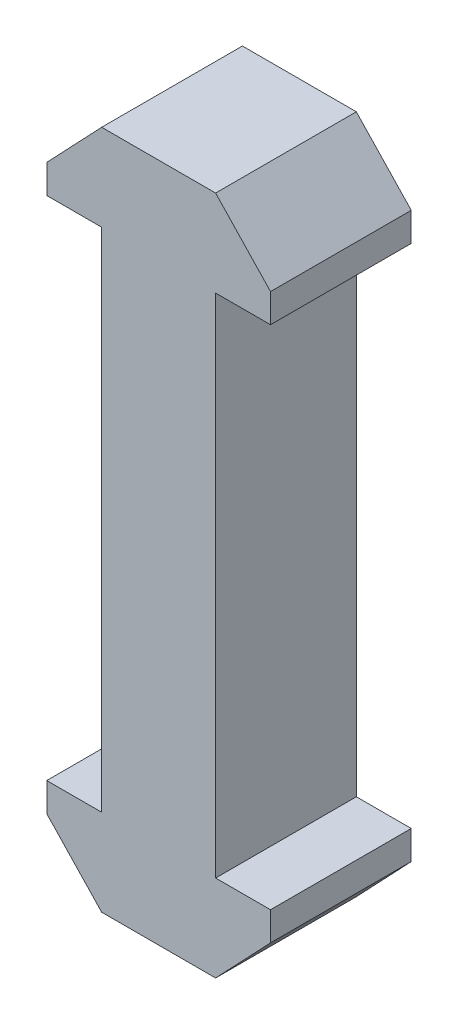
SolidWorks part; units mm, degrees
ref_plane "Front Plane" through (0, 0, 0) normal (0, 0, 1) x (1, 0, 0)
ref_plane "Top Plane" through (0, 0, 0) normal (0, 1, 0) x (1, 0, 0)
ref_plane "Right Plane" through (0, 0, 0) normal (1, 0, 0) x (0, 0, -1)
sketch "Sketch1" plane through (0, 0, 0) normal (0, 0, 1) x (1, 0, 0)
  line L3 (0, 0) -> (0, 18) construction
  line L8 (0, 18) -> (-8.6643, 18) construction
  line L14 (-4.05, 0) -> (-4.05, 36)
  line L15 (4.05, 0) -> (4.05, 36)
  point P5 (-4.05, 18)
  point P6 (4.05, 18)
  line B0 (7.95, 0) -> (7.95, -2.04)
  line B1 (4.048, -6.1524) -> (-4.048, -6.1524)
  line B2 (-7.95, -2.04) -> (-7.95, 0)
  line B3 (-7.95, 0) -> (7.95, 0)
  line B4 (7.95, -2.04) -> (4.048, -6.1524)
  line B5 (-4.048, -6.1524) -> (-7.95, -2.04)
  line B6 (4.05, 0) -> (-4.05, 0) construction
  line B7 (7.95, 36) -> (7.95, 38.04)
  line B8 (4.048, 42.1524) -> (-4.048, 42.1524)
  line B9 (-7.95, 38.04) -> (-7.95, 36)
  line B10 (-7.95, 36) -> (7.95, 36)
  line B11 (7.95, 38.04) -> (4.048, 42.1524)
  line B12 (-4.048, 42.1524) -> (-7.95, 38.04)
  line B13 (4.05, 36) -> (-4.05, 36) construction
  dimension "D1" = 36
sketch_block_instance "Block1-1"
sketch_block "Block1" parameters "D1"=8.44, "D2"=2.6, "D3"=6, "D4"=16.7, "D6"=5.6686, "D7"=2.0404, "D8"=8.0963, "D9"=15.9, "D5"=2.4157
sketch_block_instance "Block1-5"
extrude "Boss-Extrude1" add sketch "Sketch1" along normal mid plane 10 contours B0 | B0 | B12 B9 B10 B7 B11 B8 | B10 L14 B3 L15 region at (0, -2.7416, 0) region at (0, 18, 0) region at (0, 38.7416, 0)
